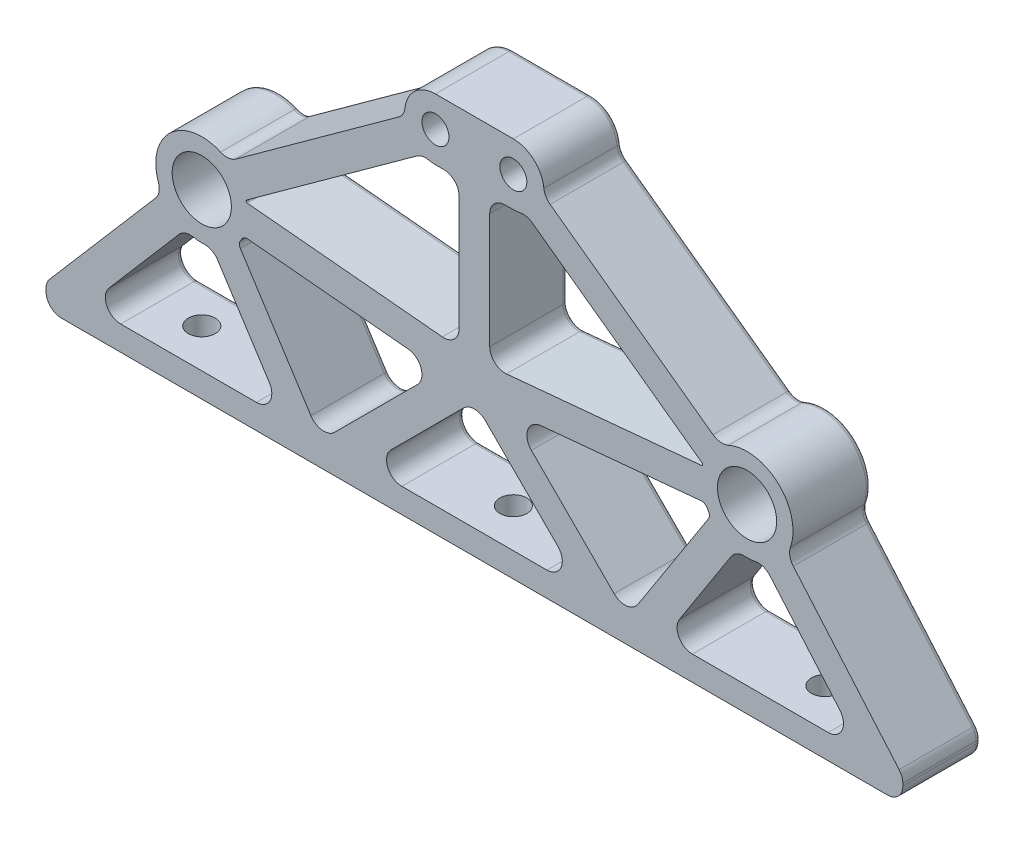
SolidWorks part; units mm, degrees
ref_plane "Front Plane" through (0, 0, 0) normal (0, 0, 1) x (1, 0, 0)
ref_plane "Top Plane" through (0, 0, 0) normal (0, 1, 0) x (1, 0, 0)
ref_plane "Right Plane" through (0, 0, 0) normal (1, 0, 0) x (0, 0, -1)
sketch "Sketch1" plane through (0, 0, 0) normal (0, 0, 1) x (1, 0, 0)
  line L0 (0, 0) -> (60.4965, 0) construction
  circle A0 centre (0, 0) radius 25.4 construction
  circle A1 centre (44.45, 35.921) radius 31.75 construction
  circle A2 centre (133.35, 35.921) radius 31.75 construction
  circle A3 centre (177.8, 0) radius 25.4 construction
  circle A4 centre (222.25, 35.921) radius 31.75 construction
  circle A5 centre (311.15, 35.921) radius 31.75 construction
  circle A6 centre (355.6, 0) radius 25.4 construction
  circle A7 centre (0, 0) radius 50.8 construction
  circle A8 centre (355.6, 0) radius 50.8 construction
  circle A9 centre (177.8, 0) radius 50.8 construction
  circle A10 centre (88.9, 35.921) radius 12.7 construction
  circle A11 centre (266.7, 35.921) radius 12.7 construction
  point P20 (-50.8, 0)
  point P21 (406.4, 0)
  dimension "D1" = 50.8
  dimension "D2" = 63.5
  dimension "D4" = 101.6
  dimension "D5" = 25.4
  dimension "D6" = 25.4
  dimension "D3" = 355.6
  dimension "D7" = 177.8
  dimension "D8" = 177.8
  dimension "D9" = 457.2
  dimension "D10" = 44.45
sketch "Sketch2" plane through (0, 0, 0) normal (0, 0, 1) x (1, 0, 0)
  line L0 (-200000, 0) -> (200060.4965, 0) construction
  line L1 (-44.45, 6.35) -> (400.05, 6.35) construction
  line L2 (-44.45, 6.35) -> (-44.45, -19.05) construction
  line L3 (-44.45, -19.05) -> (400.05, -19.05) construction
  line L4 (400.05, 6.35) -> (400.05, -19.05) construction
  circle A0 centre (-38.1, 0) radius 2.25 construction
  circle A2 centre (-31.75, -6.35) radius 2.25 construction
  circle A3 centre (-25.4, 0) radius 2.25 construction
  circle A4 centre (-12.7, 0) radius 2.25 construction
  circle A5 centre (0, 0) radius 2.25 construction
  circle A6 centre (12.7, 0) radius 2.25 construction
  circle A7 centre (25.4, 0) radius 2.25 construction
  circle A8 centre (38.1, 0) radius 2.25 construction
  circle A9 centre (50.8, 0) radius 2.25 construction
  circle A10 centre (63.5, 0) radius 2.25 construction
  circle A11 centre (76.2, 0) radius 2.25 construction
  circle A12 centre (88.9, 0) radius 2.25 construction
  circle A13 centre (101.6, 0) radius 2.25 construction
  circle A14 centre (114.3, 0) radius 2.25 construction
  circle A15 centre (127, 0) radius 2.25 construction
  circle A16 centre (139.7, 0) radius 2.25 construction
  circle A17 centre (152.4, 0) radius 2.25 construction
  circle A18 centre (165.1, 0) radius 2.25 construction
  circle A19 centre (177.8, 0) radius 2.25 construction
  circle A20 centre (190.5, 0) radius 2.25 construction
  circle A21 centre (203.2, 0) radius 2.25 construction
  circle A22 centre (215.9, 0) radius 2.25 construction
  circle A23 centre (228.6, 0) radius 2.25 construction
  circle A24 centre (241.3, 0) radius 2.25 construction
  circle A25 centre (254, 0) radius 2.25 construction
  circle A26 centre (266.7, 0) radius 2.25 construction
  circle A27 centre (279.4, 0) radius 2.25 construction
  circle A28 centre (292.1, 0) radius 2.25 construction
  circle A29 centre (304.8, 0) radius 2.25 construction
  circle A30 centre (317.5, 0) radius 2.25 construction
  circle A31 centre (330.2, 0) radius 2.25 construction
  circle A32 centre (342.9, 0) radius 2.25 construction
  circle A33 centre (355.6, 0) radius 2.25 construction
  circle A34 centre (368.3, 0) radius 2.25 construction
  circle A35 centre (381, 0) radius 2.25 construction
  circle A36 centre (393.7, 0) radius 2.25 construction
  circle A37 centre (-25.4, -12.7) radius 2.25 construction
  circle A38 centre (-12.7, -12.7) radius 2.25 construction
  circle A39 centre (0, -12.7) radius 2.25 construction
  circle A40 centre (12.7, -12.7) radius 2.25 construction
  circle A41 centre (25.4, -12.7) radius 2.25 construction
  circle A42 centre (38.1, -12.7) radius 2.25 construction
  circle A43 centre (50.8, -12.7) radius 2.25 construction
  circle A44 centre (63.5, -12.7) radius 2.25 construction
  circle A45 centre (76.2, -12.7) radius 2.25 construction
  circle A46 centre (88.9, -12.7) radius 2.25 construction
  circle A47 centre (101.6, -12.7) radius 2.25 construction
  circle A48 centre (114.3, -12.7) radius 2.25 construction
  circle A49 centre (127, -12.7) radius 2.25 construction
  circle A50 centre (139.7, -12.7) radius 2.25 construction
  circle A51 centre (152.4, -12.7) radius 2.25 construction
  circle A52 centre (165.1, -12.7) radius 2.25 construction
  circle A53 centre (177.8, -12.7) radius 2.25 construction
  circle A54 centre (190.5, -12.7) radius 2.25 construction
  circle A55 centre (203.2, -12.7) radius 2.25 construction
  circle A56 centre (215.9, -12.7) radius 2.25 construction
  circle A57 centre (228.6, -12.7) radius 2.25 construction
  circle A58 centre (241.3, -12.7) radius 2.25 construction
  circle A59 centre (254, -12.7) radius 2.25 construction
  circle A60 centre (266.7, -12.7) radius 2.25 construction
  circle A61 centre (279.4, -12.7) radius 2.25 construction
  circle A62 centre (292.1, -12.7) radius 2.25 construction
  circle A63 centre (304.8, -12.7) radius 2.25 construction
  circle A64 centre (317.5, -12.7) radius 2.25 construction
  circle A65 centre (330.2, -12.7) radius 2.25 construction
  circle A66 centre (342.9, -12.7) radius 2.25 construction
  circle A67 centre (355.6, -12.7) radius 2.25 construction
  circle A68 centre (368.3, -12.7) radius 2.25 construction
  circle A69 centre (381, -12.7) radius 2.25 construction
  circle A70 centre (393.7, -12.7) radius 2.25 construction
  circle A71 centre (-38.1, -12.7) radius 2.25 construction
  circle A72 centre (-19.05, -6.35) radius 2.25 construction
  circle A73 centre (-6.35, -6.35) radius 2.25 construction
  circle A74 centre (6.35, -6.35) radius 2.25 construction
  circle A75 centre (19.05, -6.35) radius 2.25 construction
  circle A76 centre (31.75, -6.35) radius 2.25 construction
  circle A77 centre (44.45, -6.35) radius 2.25 construction
  circle A78 centre (57.15, -6.35) radius 2.25 construction
  circle A79 centre (69.85, -6.35) radius 2.25 construction
  circle A80 centre (82.55, -6.35) radius 2.25 construction
  circle A81 centre (95.25, -6.35) radius 2.25 construction
  circle A82 centre (107.95, -6.35) radius 2.25 construction
  circle A83 centre (120.65, -6.35) radius 2.25 construction
  circle A84 centre (133.35, -6.35) radius 2.25 construction
  circle A85 centre (146.05, -6.35) radius 2.25 construction
  circle A86 centre (158.75, -6.35) radius 2.25 construction
  circle A87 centre (171.45, -6.35) radius 2.25 construction
  circle A88 centre (184.15, -6.35) radius 2.25 construction
  circle A89 centre (196.85, -6.35) radius 2.25 construction
  circle A90 centre (209.55, -6.35) radius 2.25 construction
  circle A91 centre (222.25, -6.35) radius 2.25 construction
  circle A92 centre (234.95, -6.35) radius 2.25 construction
  circle A93 centre (247.65, -6.35) radius 2.25 construction
  circle A94 centre (260.35, -6.35) radius 2.25 construction
  circle A95 centre (273.05, -6.35) radius 2.25 construction
  circle A96 centre (285.75, -6.35) radius 2.25 construction
  circle A97 centre (298.45, -6.35) radius 2.25 construction
  circle A98 centre (311.15, -6.35) radius 2.25 construction
  circle A99 centre (323.85, -6.35) radius 2.25 construction
  circle A100 centre (336.55, -6.35) radius 2.25 construction
  circle A101 centre (349.25, -6.35) radius 2.25 construction
  circle A102 centre (361.95, -6.35) radius 2.25 construction
  circle A103 centre (374.65, -6.35) radius 2.25 construction
  circle A104 centre (387.35, -6.35) radius 2.25 construction
  dimension "D5" = 4.5
  dimension "D1" = 25.4
  dimension "D2" = 444.5
  dimension "D3" = 6.35
  dimension "D4" = 44.45
  dimension "D6" = 6.35
  dimension "D7" = 6.35
  dimension "D8" = 6.35
  dimension "D12" = 12.7
  dimension "D9" = 35
  dimension "D10" = 2
  dimension "D11" = 34
sketch "Sketch3" plane through (0, 0, 0) normal (0, 0, 1) x (1, 0, 0)
  line L0 (44.45, 35.921) -> (88.9, 31.75) construction
  line L1 (88.9, 31.75) -> (133.35, 35.921) construction
  line L2 (44.45, 35.921) -> (19.05, 6.35) construction
  line L3 (-44.45, 6.35) -> (400.05, 6.35) construction
  line L4 (19.05, 6.35) -> (158.75, 6.35) construction
  line L5 (158.75, 6.35) -> (133.35, 35.921) construction
  line L6 (44.45, 35.921) -> (63.5, 6.35) construction
  line L7 (63.5, 6.35) -> (88.9, 31.75) construction
  line L8 (88.9, 31.75) -> (114.3, 6.35) construction
  line L9 (114.3, 6.35) -> (133.35, 35.921) construction
  line L10 (19.05, 6.35) -> (158.75, 6.35)
  line L11 (158.75, 6.35) -> (158.75, 10.1868)
  line L12 (158.75, 10.1868) -> (139.8538, 32.186)
  line L13 (88.9, 34.261) -> (126.0763, 37.7495)
  line L14 (126.5434, 32.7713) -> (94.4278, 29.7577)
  line L15 (152.0186, 10.35) -> (119.8507, 10.35)
  line L16 (119.8507, 10.35) -> (131.6222, 28.6228)
  line L17 (152.0186, 10.35) -> (136.0609, 28.9281)
  line L18 (113.8766, 10.309) -> (127.4189, 31.3306)
  line L19 (113.8766, 10.309) -> (94.4278, 29.7577)
  line L20 (106.7645, 10.35) -> (71.0355, 10.35)
  line L21 (71.0355, 10.35) -> (88.9, 28.2145)
  line L22 (106.7645, 10.35) -> (88.9, 28.2145)
  line L24 (51.2566, 32.7713) -> (83.3722, 29.7577)
  line L26 (25.7814, 10.35) -> (57.9493, 10.35)
  line L27 (57.9493, 10.35) -> (46.1778, 28.6228)
  line L28 (25.7814, 10.35) -> (41.7391, 28.9281)
  line L29 (19.05, 6.35) -> (19.05, 10.1868)
  line L30 (19.05, 10.1868) -> (37.9462, 32.186)
  line L31 (51.7237, 37.7495) -> (88.9, 34.261)
  line L32 (63.9234, 10.309) -> (50.3811, 31.3306)
  line L33 (63.9234, 10.309) -> (83.3722, 29.7577)
  circle A0 centre (44.45, 35.921) radius 4.826
  circle A2 centre (133.35, 35.921) radius 4.826
  circle A3 centre (44.45, 35.921) radius 7.5
  circle A5 centre (133.35, 35.921) radius 7.5
  circle A6 centre (44.45, 35.921) radius 2.5
  circle A7 centre (133.35, 35.921) radius 2.5
  dimension "D1" = 9.652
  dimension "D2" = 15
  dimension "D3" = 5
  dimension "D20" = 5
  dimension "Thickness" = 5
  dimension "D4" = 2.5
  dimension "D5" = 2.5
  dimension "D6" = 5
  dimension "D7" = 2.5
  dimension "D8" = 5
  dimension "D9" = 2.5
  dimension "D10" = 5
  dimension "D11" = 5
  dimension "D12" = 2.5
  dimension "D13" = 4
  dimension "D14" = 2.5
  dimension "D15" = 5
  dimension "D16" = 5
  dimension "D17" = 5
  dimension "D18" = 2.5
  dimension "D19" = 25.4
extrude "Boss-Extrude1" add sketch "Sketch3" along normal blind 12.7 contours A5 L13 L31 A3 L24 L33 L32 L27 L26 L28 L30 L29 L10 L11 L12 L17 L15 L16 L18 L19 L14 L22 L20 L21 | A3 A0 | A5 A2 region at (20.4819, 8.2684, 0) region at (41.7212, 42.6787, 0) region at (138.0986, 30.3926, 0)
sketch "Sketch5" plane through (0, 0, 0) normal (0, 0, -1) x (-1, 0, 0)
  line L0 (-88.9, 34.261) -> (-88.9, 11.7037) construction
  line L1 (-95.25, 63.5) -> (-82.55, 63.5) construction
  line L2 (-95.25, 68.5) -> (-82.55, 68.5)
  line L3 (-95.25, 58.5) -> (-82.55, 58.5)
  line L4 (-19.05, 6.35) -> (-158.75, 6.35) construction
  line L5 (-51.7237, 37.7495) -> (-88.9, 34.261) construction
  line L6 (-88.9, 34.261) -> (-126.0763, 37.7495) construction
  line L7 (-51.7237, 37.7495) -> (-88.9, 34.261)
  line L8 (-88.9, 34.261) -> (-126.0763, 37.7495)
  line L9 (-91.4, 34.4956) -> (-91.4, 58.5)
  line L10 (-86.4, 34.4956) -> (-86.4, 58.5)
  line L11 (-126.1562, 38.0421) -> (-97.2917, 58.9359)
  line L12 (-129.088, 42.0923) -> (-100.2235, 62.9861)
  line L13 (-80.5083, 58.9359) -> (-51.6438, 38.0421)
  line L14 (-48.712, 42.0923) -> (-77.5765, 62.9861)
  line L15 (-133.35, 35.921) -> (-95.25, 63.5) construction
  line L16 (-82.55, 63.5) -> (-44.45, 35.921) construction
  arc A2 (-37.9462, 32.186) -> (-51.7237, 37.7495) centre (-44.45, 35.921) ccw construction
  arc A3 (-126.0763, 37.7495) -> (-139.8538, 32.186) centre (-133.35, 35.921) ccw construction
  arc A4 (-37.9462, 32.186) -> (-51.7237, 37.7495) centre (-44.45, 35.921) ccw
  arc A5 (-126.0763, 37.7495) -> (-139.8538, 32.186) centre (-133.35, 35.921) ccw
  arc A6 (-95.25, 68.5) -> (-95.25, 58.5) centre (-95.25, 63.5) ccw
  arc A7 (-82.55, 58.5) -> (-82.55, 68.5) centre (-82.55, 63.5) ccw
  circle A8 centre (-95.25, 63.5) radius 2.2
  circle A9 centre (-82.55, 63.5) radius 2.2
  point P0 (-88.9, 34.261)
  point P3 (-133.35, 35.921)
  point P4 (-44.45, 35.921)
  point P5 (-88.9, 63.5)
  point P10 (-88.9, 6.35)
  point P40 (0, 0)
  point P41 (0, 0)
  point P42 (0, 0)
  point P44 (0, 0)
  line M16 (-51.7237, 37.7495) -> (-88.9, 34.261)
  line M17 (-88.9, 34.261) -> (-126.0763, 37.7495)
  arc M18 (-126.0763, 37.7495) -> (-139.8538, 32.186) centre (-133.35, 35.921) ccw
  arc M24 (-37.9462, 32.186) -> (-51.7237, 37.7495) centre (-44.45, 35.921) ccw
  dimension "D5" = 10
  dimension "D6" = 57.15
  dimension "D7" = 4.4
  dimension "D1" = 12.7
  dimension "D2" = 5
  dimension "D3" = 5
  dimension "D4" = 5
extrude "Boss-Extrude3" add sketch "Sketch5" against normal blind 12.7 contours L9 L7 L10 M17 | L12 L11 M18 M17 | L13 L14 M16 M24 | L3 A7 L2 A6 A9 A8 region at (88.9, 63.5, 0) region at (113.2565, 50.4658, 0) region at (64.5435, 50.4658, 0) region at (88.9, 46.439, 0)
fillet "Fillet1" radius 2.5 31 edges at (158.75, 6.35, 6.35) (158.75, 10.1868, 6.35) (19.05, 6.35, 6.35) (19.05, 10.1868, 6.35) (139.8538, 32.186, 6.35) (152.0186, 10.35, 6.35) (136.0609, 28.9281, 6.35) (131.6222, 28.6228, 6.35) (119.8507, 10.35, 6.35) (113.8766, 10.309, 6.35) (106.7645, 10.35, 6.35) (25.7814, 10.35, 6.35) (41.7391, 28.9281, 6.35) (46.1778, 28.6228, 6.35) (57.9493, 10.35, 6.35) (71.0355, 10.35, 6.35) (63.9234, 10.309, 6.35) (37.9462, 32.186, 6.35) (88.9, 28.2145, 6.35) (94.4278, 29.7577, 6.35) (83.3722, 29.7577, 6.35) (91.4, 34.4956, 6.35) (86.4, 34.4956, 6.35) (129.088, 42.0923, 6.35) (48.712, 42.0923, 6.35) (100.2235, 62.9861, 6.35) (77.5765, 62.9861, 6.35) (80.5083, 58.9359, 6.35) (86.4, 58.5, 6.35) (91.4, 58.5, 6.35) (97.2917, 58.9359, 6.35)
fillet "Fillet5" radius 0.2 4 edges at (126.0763, 37.7495, 6.35) (126.1562, 38.0421, 6.35) (51.7237, 37.7495, 6.35) (51.6438, 38.0421, 6.35)
fillet "Fillet6" radius 1 4 edges at (50.3811, 31.3306, 6.35) (51.2566, 32.7713, 6.35) (126.5434, 32.7713, 6.35) (127.4189, 31.3306, 6.35)
sketch "Sketch4" plane through (0, 6.35, 0) normal (0, -1, 0) x (1, 0, 0)
  line L0 (21.55, 12.7) -> (21.55, 0) construction
  circle A0 centre (38.1, 6.35) radius 2.2
  circle A1 centre (88.9, 6.35) radius 2.2
  circle A2 centre (139.7, 6.35) radius 2.2
  point P0 (139.7, 0)
  point P2 (88.9, 0)
  point P4 (38.1, 0)
  point P15 (21.55, 6.35)
  dimension "D1" = 4.4
extrude "Cut-Extrude1" cut sketch "Sketch4" against normal up to next
extrude "Boss-Extrude2" add sketch "Sketch3<3>" along normal blind 3.175 contours A0 | A2 region at (39.7605, 35.921, 0) region at (128.6605, 35.921, 0)
sketch "Sketch3<3>" plane through (0, 0, 0) normal (0, 0, 1) x (1, 0, 0) same geometry as "Sketch3"
fillet "Fillet2" radius 0.75 86 edges at (135.85, 35.921, 0) (46.95, 35.921, 0) (74.7614, 11.8933, 0) (81.2178, 20.5322, 0) (88.9, 27.1789, 0) (96.5822, 20.5322, 0) (103.0386, 11.8933, 0) (88.9, 10.35, 0) (136.0279, 28.4526, 0) (142.7842, 21.1008, 0) (148.8474, 11.8065, 0) (135.5053, 10.35, 0) (122.2402, 11.6531, 0) (126.5475, 20.7453, 0) (131.7201, 28.1562, 0) (133.8647, 28.4387, 0) (46.0799, 28.1562, 0) (51.2525, 20.7453, 0) (55.5598, 11.6531, 0) (42.2947, 10.35, 0) (28.9526, 11.8065, 0) (35.0158, 21.1008, 0) (41.7721, 28.4526, 0) (43.9353, 28.4387, 0) (65.0032, 31.4814, 0) (80.1963, 28.6131, 0) (72.8634, 19.2489, 0) (64.081, 11.7821, 0) (56.4959, 21.8386, 0) (158.5943, 10.1291, 0) (149.5179, 20.935, 0) (140.3289, 32.1469, 0) (138.4284, 41.4401, 0) (110.0352, 36.2442, 0) (67.7648, 36.2442, 0) (39.3716, 41.4401, 0) (37.4711, 32.1469, 0) (28.2821, 20.935, 0) (19.2057, 10.1291, 0) (19.05, 9.0553, 0) (19.7822, 7.0822, 0) (88.9, 6.35, 0) (158.0178, 7.0822, 0) (158.75, 9.0553, 0) (121.3041, 21.8386, 0) (113.719, 11.7821, 0) (104.9366, 19.2489, 0) (97.6037, 28.6131, 0) (112.7968, 31.4814, 0) (86.4, 46.6206, 0) (65.6224, 48.1606, 0) (114.5224, 52.6357, 0) (63.2776, 52.6357, 0) (112.1776, 48.1606, 0) (91.4, 46.6206, 0) (85.5832, 35.3926, 0) (129.0096, 42.5625, 0) (48.7904, 42.5625, 0) (92.2168, 35.3926, 0) (93.05, 63.5, 0) (80.35, 63.5, 0) (83.225, 58.5, 0) (88.9, 68.5, 0) (79.2015, 67.2131, 0) (95.7852, 58.5287, 0) (80.4421, 58.619, 0) (82.0148, 58.5287, 0) (85.6678, 57.7678, 0) (100.5452, 63.0222, 0) (98.5985, 67.2131, 0) (77.2548, 63.0222, 0) (92.1322, 57.7678, 0) (94.575, 58.5, 0) (97.3579, 58.619, 0) (50.5872, 31.3057, 0) (50.8594, 32.0263, 0) (51.3736, 32.5998, 0) (51.6858, 38.0285, 0) (51.753, 37.7825, 0) (51.6852, 37.8962, 0) (127.2128, 31.3057, 0) (126.4264, 32.5998, 0) (126.9406, 32.0263, 0) (126.1142, 38.0285, 0) (126.1148, 37.8962, 0) (126.047, 37.7825, 0)
